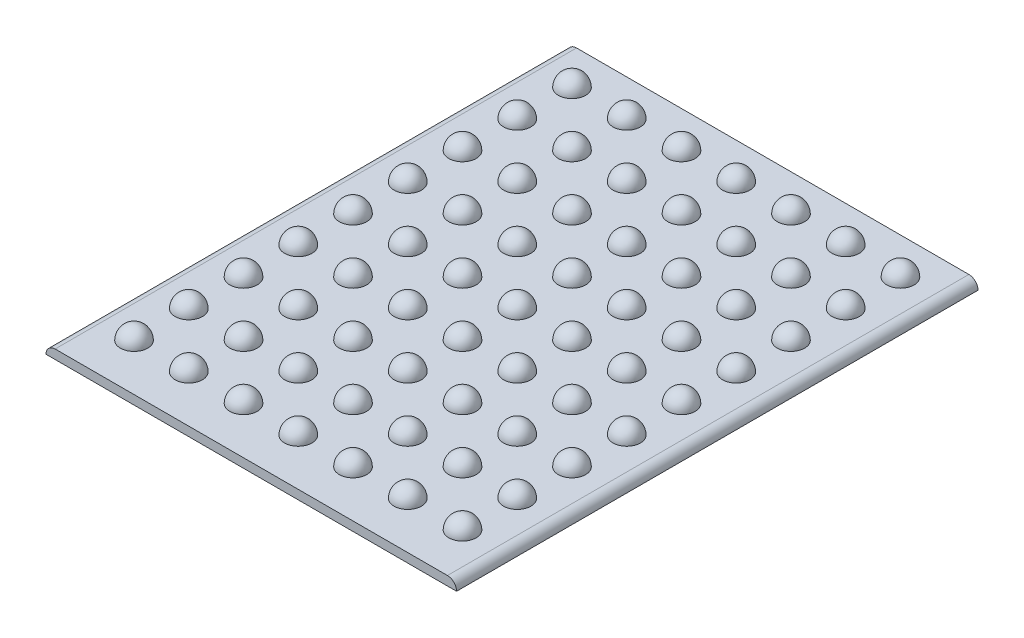
SolidWorks part; units mm, degrees
ref_plane "Front Plane" through (0, 0, 0) normal (0, 0, 1) x (1, 0, 0)
ref_plane "Top Plane" through (0, 0, 0) normal (0, 1, 0) x (1, 0, 0)
ref_plane "Right Plane" through (0, 0, 0) normal (1, 0, 0) x (0, 0, -1)
sketch "Sketch1" plane through (0, 0, 0) normal (0, 1, 0) x (1, 0, 0)
  line L1 (0, 114.3) -> (90, 114.3)
  line L2 (0, 114.3) -> (0, 0)
  line L3 (0, 0) -> (90, 0)
  line L4 (90, 114.3) -> (90, 0)
  dimension "D1" = 90
  dimension "D2" = 114.3
extrude "Boss-Extrude1" add sketch "Sketch1" along normal blind 2
sketch "Sketch2" plane through (0, 2, 0) normal (0, 1, 0) x (1, 0, 0)
  line L0 (9, 110.669) -> (9, 101.931) construction
  line L1 (9, 109.3) -> (9, 103.3)
  line L2 (90, 114.3) -> (0, 114.3) construction
  line L3 (0, 114.3) -> (0, 0) construction
  arc A0 (9, 103.3) -> (9, 109.3) centre (9, 106.3) cw
  dimension "D1" = 3
  dimension "D2" = 8
  dimension "D3" = 9
revolve "Revolve1" add sketch "Sketch2" angle 180 about L0 reverse direction yes
pattern_linear "LPattern1" count 7 spacing 12 along (1, 0, 0) count 9 spacing 12 along (0, 0, 1) of "Revolve1"
fillet "Fillet1" radius 2 2 edges at (0, 2, -57.15) (90, 2, -57.15)
